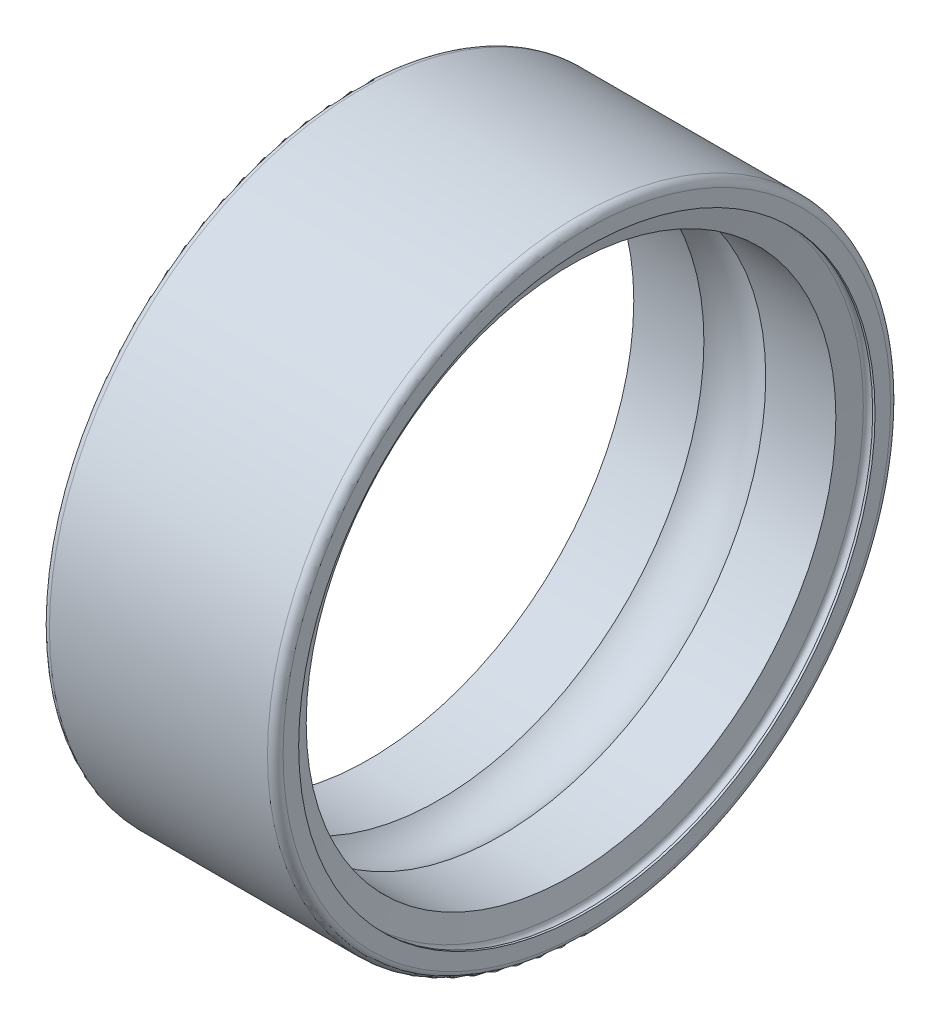
SolidWorks part; units mm, degrees
ref_plane "Ebene vorne" through (0, 0, 0) normal (0, 0, 1) x (1, 0, 0)
ref_plane "Ebene oben" through (0, 0, 0) normal (0, 1, 0) x (1, 0, 0)
ref_plane "Ebene rechts" through (0, 0, 0) normal (1, 0, 0) x (0, 0, -1)
ref_plane "Plane1" through (0, 0, 0) normal (0, 0, 1) x (1, 0, 0)
sketch "Sketch1" plane through (0, 0, 0) normal (0, 0, 1) x (1, 0, 0)
  line L0 (0, 3.9) -> (0, 3.7)
  line L1 (0, 3.7) -> (0.03, 3.7)
  line L2 (0.15, 3.7) -> (0.2029, 3.4)
  line L3 (0.2029, 3.4) -> (1.1031, 3.4)
  line L4 (1.8969, 3.4) -> (2.7971, 3.4)
  line L5 (2.7971, 3.4) -> (2.85, 3.7)
  line L6 (2.97, 3.7) -> (3, 3.7)
  line L7 (3, 3.7) -> (3, 3.9)
  line L8 (2.9, 4) -> (0.1, 4)
  line L9 (50, 0) -> (-50, 0) construction
  arc A0 (0.03, 3.7) -> (0.15, 3.7) centre (0.09, 3.7) cw
  arc A1 (1.1031, 3.4) -> (1.8969, 3.4) centre (1.5, 2.95) cw
  arc A2 (2.85, 3.7) -> (2.97, 3.7) centre (2.91, 3.7) cw
  arc A3 (3, 3.9) -> (2.9, 4) centre (2.9, 3.9) ccw
  arc A4 (0.1, 4) -> (0, 3.9) centre (0.1, 3.9) ccw
revolve "Revolve1" add sketch "Sketch1" angle 360 about L9 reverse direction yes
